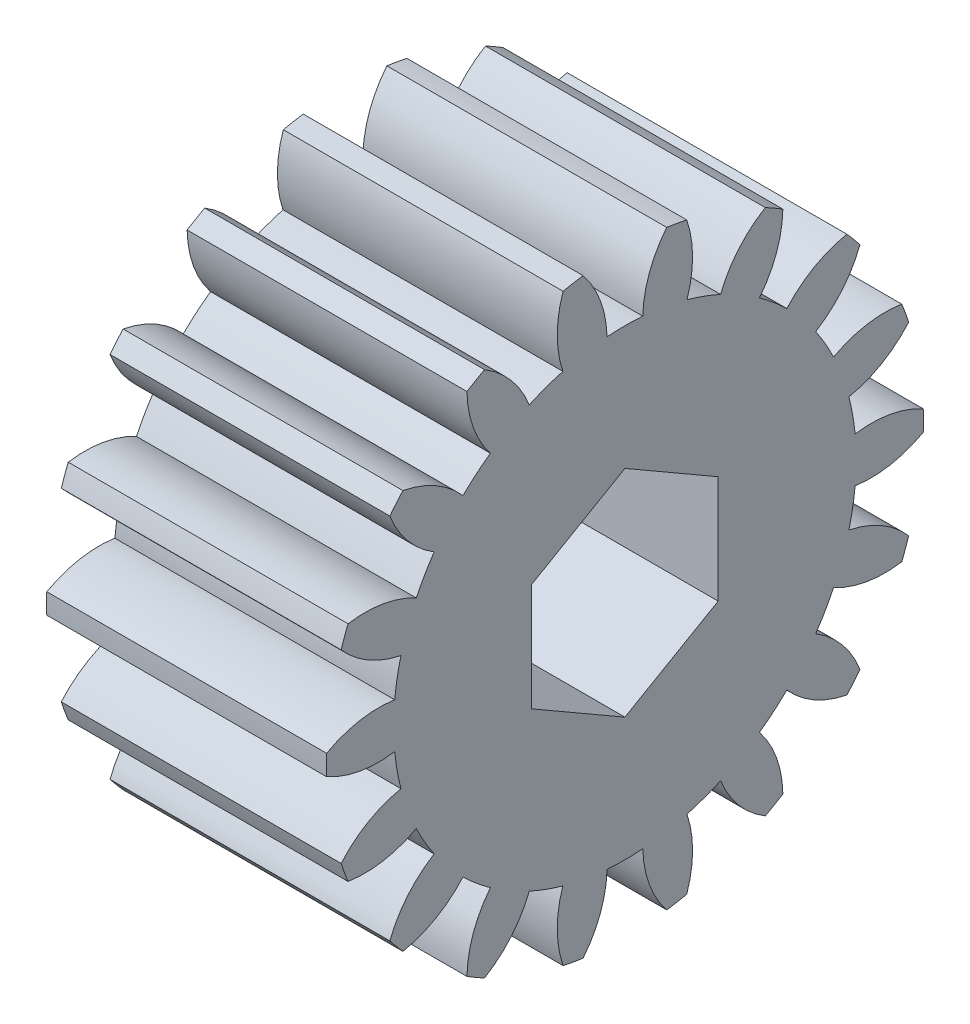
SolidWorks part; units mm, degrees
ref_plane "Plane1" through (0, 0, 0) normal (0, 0, 1) x (1, 0, 0)
ref_plane "Plane2" through (0, 0, 0) normal (0, 1, 0) x (1, 0, 0)
ref_plane "Plane3" through (0, 0, 0) normal (1, 0, 0) x (0, 0, -1)
other "Configuration Table"
sketch "HoldingSke" plane through (0, 0, 0) normal (0, 1, 0) x (1, 0, 0)
  line L0 (0, 0) -> (1.1888, -0.3863)
  line L1 (-15, 0) -> (100, 0) construction
  line L2 (0, 0) -> (-2.1039, 2.3779)
  line L3 (0, 0) -> (-11.863, 4.5341)
  line L4 (0, 0) -> (8.2133, 2.6687)
  line L5 (0, 0) -> (-46.8476, -17.4728)
  line L6 (0, 0) -> (-6.2172, -4.1948)
  line L7 (-2.1039, 2.3779) -> (8.6586, 51.2059)
  line L8 (-76.2, 54.61) -> (-75.3, 54.61)
  line L9 (-67.7845, 28.3722) -> (-49.3413, 33.142)
  line L10 (-76.2, 71.12) -> (104.1128, 71.12)
  line L11 (0, 0) -> (-7.5, 0)
  line L12 (-76.2, 101.6) -> (-76.17, 101.6)
  line L13 (24.9733, 27.94) -> (52.9518, 28.4284)
  line L14 (24.9733, 27.94) -> (24.9743, 27.94)
  line L15 (24.9733, 27.94) -> (100.4006, 29.5858)
  line L16 (-63.627, -0.8) -> (-12.827, -0.8)
  circle A0 centre (0, 0) radius 2.5
  circle A1 centre (0, 0) radius 6.199
  circle A2 centre (0, 0) radius 37.5
  circle A3 centre (0, 0) radius 2.5
  dimension "MHD" = 12.398
  dimension "Hub_dia" = 75
  dimension "Bore" = 5
  dimension "MBD" = 5
  dimension "Num_teeth" = 18
  dimension "Pitch" = 1.25
  dimension "Overall_len" = 50
  dimension "Show_teeth" = 18
  dimension "Thickness" = 7.5
  dimension "OAL" = 50.0001
  dimension "T_dim" = 0.9
  dimension "Ap" = 14.5
  dimension "H" = 19.05
  dimension "Pitch_radius" = 180.3128
  dimension "Width" = 7.5
  dimension "Backlash" = 0.03
  dimension "Addendum_fac" = 1
  dimension "Dedendum_fac" = 1.25
  dimension "Clearance_fac" = 0.25
  dimension "Dedendum_add" = 0.001
  dimension "Module" = 0.8
sketch "BasProSke" plane through (0, 0, 0) normal (0, 1, 0) x (1, 0, 0)
  line L0 (-10, 0) -> (60, 0) construction
  line L1 (0, 0) -> (0, 8)
  line L2 (0, 0) -> (7.5, 0)
  line L3 (7.5, 0) -> (7.5, 8)
  line L4 (7.5, 8) -> (0, 8)
  dimension "Thickness" = 7.5
  dimension "Diameter" = 16
revolve "Base-Revolve" add sketch "BasProSke" angle 360 about L0
sketch "TooCutSke" plane through (0, 0, 0) normal (1, 0, 0) x (0, 0, -1)
  line L1 (0, 0) -> (0, 107) construction
  line L2 (0, 0) -> (-0.68, 7.1678) construction
  line L3 (0, 0) -> (-2.4925, 14.1359) construction
  line L4 (-0.68, 7.1678) -> (-1.2463, 7.068) construction
  arc A0 (0.479, 6.1805) -> (-0.479, 6.1805) centre (0, 0) ccw
  arc A1 (1.1389, 7.9442) -> (-1.1389, 7.9442) centre (0, 0) ccw
  circle A2 centre (0, 0) radius 7.2 construction
  circle A3 centre (0, 0) radius 6.9707 construction
  arc A4 (-0.479, 6.1805) -> (-1.1389, 7.9442) centre (-3.3581, 6.1085) ccw
  arc A5 (1.1389, 7.9442) -> (0.479, 6.1805) centre (3.3581, 6.1085) ccw
  dimension "Root_dia" = 12.398
  dimension "Overcut_dia" = 16.0508
  dimension "Pitch_dia" = 14.4
  dimension "Base_dia" = 13.9413
  dimension "Flank_rad" = 2.88
  dimension "Half_ang" = 10
  dimension "Half_CT" = 0.575
extrude "ToothCut" cut sketch "TooCutSke" along normal through all
fillet "Breaks" [suppressed] radius 0.016 tangent propagation no
fillet "RootFillets" [suppressed] radius 0.201
pattern_circular "TeethCuts" count 18 every 20 about axis through (-10, 0, 0) along (1, 0, 0) of "ToothCut", "RootFillets", "Breaks"
sketch "HubNeaOneSke" plane through (0, 0, 0) normal (-1, 0, 0) x (0, 0, 1)
  circle A0 centre (0, 0) radius 6.199
  dimension "Diameter" = 12.398
extrude "HubNearOne" [suppressed] add sketch "HubNeaOneSke" along normal blind 42.5001
sketch "HubNeaBotSke" plane through (0, 0, 0) normal (-1, 0, 0) x (0, 0, 1)
  circle A0 centre (0, 0) radius 6.199
  dimension "Diameter" = 12.398
extrude "HubNearBoth" [suppressed] add sketch "HubNeaBotSke" along normal blind 21.25
ref_plane "FarPln" through (7.5, 0, 0) normal (1, 0, 0) x (0, 0, -1)
sketch "HubFarSke" plane through (7.5, 0, 0) normal (1, 0, 0) x (0, 0, -1)
  circle A0 centre (0, 0) radius 6.199
  dimension "Diameter" = 12.398
extrude "HubFar" [suppressed] add sketch "HubFarSke" along normal blind 21.25
sketch "BorSke" plane through (0, 0, 0) normal (1, 0, 0) x (0, 0, -1)
  circle A0 centre (0, 0) radius 2.5
  dimension "Diameter" = 5
extrude "Bore" cut sketch "BorSke" along normal mid plane 100.0001
sketch "KeySke" plane through (0, 0, 0) normal (1, 0, 0) x (0, 0, -1)
  line L0 (-1, 0) -> (-1, 3.4)
  line L1 (-1, 3.4) -> (1, 3.4)
  line L2 (1, 3.4) -> (1, 0)
  line L3 (0, 0) -> (0, 34) construction
  line L4 (-1, 0) -> (1, 0)
  dimension "Offset" = 3.4
  dimension "Width" = 2
extrude "Keyway" [suppressed] cut sketch "KeySke" along normal mid plane 100.0001
pattern_circular "Keyway2" [suppressed] count 2 every 90 about axis through (-10, 0, 0) along (1, 0, 0) reverse direction yes
sketch "Schizzo2" plane through (7.5, 0, 0) normal (1, 0, 0) x (0, 0, -1)
  line L1 (0, 2.8868) -> (-2.5, 1.4434)
  line L2 (-2.5, 1.4434) -> (-2.5, -1.4434)
  line L3 (-2.5, -1.4434) -> (0, -2.8868)
  line L4 (0, -2.8868) -> (2.5, -1.4434)
  line L5 (2.5, -1.4434) -> (2.5, 1.4434)
  line L6 (2.5, 1.4434) -> (0, 2.8868)
  circle A0 centre (0, 0) radius 2.5 construction
extrude "Taglio-Estrusione1" cut sketch "Schizzo2" against normal blind 10
equation "' \"Module@HoldingSke\" = 6.35"
equation "' \"Num_teeth@HoldingSke\" = 12"
equation "' \"Ap@HoldingSke\" =  20"
equation "' \"Ap@HoldingSke\" = 20"
equation "' \"Width@HoldingSke\" = 0.5 * 25.4"
equation "' \"Hub_dia@HoldingSke\"= 1 * 25.4"
equation "' \"Hub_dia@HoldingSke\" = 1 * 25.4"
equation "' \"Overall_len@HoldingSke\" = 1.0 * 25.4"
equation "' \"Bore@HoldingSke\" = 0.75 * 25.4"
equation "' \"T_dim@HoldingSke\" = 0.1 * 25.4"
equation "' \"Width@KeySke\" = 0.25 * 25.4"
equation "' \"Show_teeth@HoldingSke\" = 13"
equation "' \"Backlash@HoldingSke\" = 0.009 * 25.4"
equation "' \"Addendum_fac@HoldingSke\" = 1.0"
equation "' \"Dedendum_fac@HoldingSke\" = 1.25"
equation "' \"Dedendum_add@HoldingSke\" = 0.00005 * 25.4"
equation "' \"Clearance_fac@HoldingSke\" = 0.25"
equation "\"Pitch@HoldingSke\" = 1 / \"Module@HoldingSke\""
equation "\"Overcut_dia@TooCutSke\" = (\"Num_teeth@HoldingSke\" + 2 * \"Addendum_fac@HoldingSke\") / \"Pitch@HoldingSke\" + 0.002 * 25.4"
equation "\"Pitch_dia@TooCutSke\" = \"Num_teeth@HoldingSke\" / \"Pitch@HoldingSke\""
equation "\"Base_dia@TooCutSke\" = \"Num_teeth@HoldingSke\" / \"Pitch@HoldingSke\" * cos((\"Ap@HoldingSke\"  * 3.14159265 / 180))"
equation "\"Root_dia@TooCutSke\" = (\"Num_teeth@HoldingSke\" + 2) / \"Pitch@HoldingSke\" - 2 * (\"Addendum_fac@HoldingSke\" + \"Dedendum_fac@HoldingSke\") / \"Pitch@HoldingSke\" - \"Dedendum_add@HoldingSke\" * 2"
equation "\"Half_ang@TooCutSke\" = 180 / \"Num_teeth@HoldingSke\""
equation "\"Half_CT@TooCutSke\" = \"Num_teeth@HoldingSke\" / \"Pitch@HoldingSke\" * sin((3.14159265 / 2 / \"Num_teeth@HoldingSke\")) / 2 - 7 * \"Backlash@HoldingSke\" / 4"
equation "\"Flank_rad@TooCutSke\" = \"Num_teeth@HoldingSke\" / \"Pitch@HoldingSke\" / 5"
equation "\"Radius@RootFillets\" = \"Clearance_fac@HoldingSke\" / \"Pitch@HoldingSke\" + \"Dedendum_add@HoldingSke\""
equation "\"Break_rad@Breaks\" = 0.02 / \"Pitch@HoldingSke\""
equation "\"Thickness@HoldingSke\" = \"Width@HoldingSke\""
equation "\"OAL@HoldingSke\" = \"Thickness@HoldingSke\""
equation "\"MHD@HoldingSke\" = (\"Num_teeth@HoldingSke\" + 2) / \"Pitch@HoldingSke\" - 2 * (\"Addendum_fac@HoldingSke\" + \"Dedendum_fac@HoldingSke\")  / \"Pitch@HoldingSke\" - \"Dedendum_add@HoldingSke\" * 2"
equation "\"MBD@HoldingSke\" = (\"Num_teeth@HoldingSke\" + 2) / \"Pitch@HoldingSke\" - 2 * (\"Addendum_fac@HoldingSke\" + \"Dedendum_fac@HoldingSke\")  / \"Pitch@HoldingSke\" - \"Dedendum_add@HoldingSke\" * 2 - 0.002 * 25.4"
equation "\"MHD@HoldingSke\" = ((sgn( \"MHD@HoldingSke\" - \"Hub_dia@HoldingSke\" )-1)*( \"MHD@HoldingSke\" - \"Hub_dia@HoldingSke\" ))/-2+ \"Hub_dia@HoldingSke\""
equation "\"MBD@HoldingSke\" = ((sgn( \"MBD@HoldingSke\" - \"Bore@HoldingSke\" )-1)*( \"MBD@HoldingSke\" - \"Bore@HoldingSke\" ))/-2+ \"Bore@HoldingSke\""
equation "\"OAL@HoldingSke\" = ((sgn( \"OAL@HoldingSke\" - \"Overall_len@HoldingSke\" )+1)*( \"OAL@HoldingSke\" - \"Overall_len@HoldingSke\" ))/2 + \"Overall_len@HoldingSke\" + 0.000002 * 25.4"
equation "\"Num_teeth@TeethCuts\" = int( \"Show_teeth@HoldingSke\" ) + 1"
equation "\"Num_teeth@TeethCuts\" = ((sgn( \"Num_teeth@TeethCuts\" - \"Num_teeth@HoldingSke\" )-1)*( \"Num_teeth@TeethCuts\" - \"Num_teeth@HoldingSke\" ))/-2+ \"Num_teeth@HoldingSke\""
equation "\"Num_teeth@TeethCuts\" = ((sgn( \"Num_teeth@TeethCuts\" - 2.0)+1)*( \"Num_teeth@TeethCuts\" - 2.0))/2 +2.0"
equation "\"Angle@TeethCuts\" = 360.0 / \"Num_teeth@HoldingSke\""
equation "\"Diameter@BasProSke\" = (\"Num_teeth@HoldingSke\" + 2 * \"Addendum_fac@HoldingSke\") / \"Pitch@HoldingSke\""
equation "\"Thickness@BasProSke\"  = \"Thickness@HoldingSke\""
equation "' \"Fillet_rad@BasProSke\" =  \"Thickness@HoldingSke\" * 0.05"
equation "' \"Fillet_rad@BasProSke\" = \"Thickness@HoldingSke\" * 0.05"
equation "\"MHD@HoldingSke\" = ((sgn( \"MHD@HoldingSke\" - \"Root_dia@TooCutSke\" )-1)*( \"MHD@HoldingSke\" - \"Root_dia@TooCutSke\" ))/-2+ \"Root_dia@TooCutSke\""
equation "\"Diameter@HubNeaOneSke\" = \"MHD@HoldingSke\""
equation "\"Length@HubNearOne\" = \"OAL@HoldingSke\" - \"Thickness@BasProSke\""
equation "\"Diameter@HubNeaBotSke\" = \"MHD@HoldingSke\""
equation "\"Length@HubNearBoth\" = ( \"OAL@HoldingSke\" - \"Thickness@BasProSke\" ) / 2.0"
equation "\"Thickness@FarPln\" = \"Thickness@BasProSke\""
equation "\"Diameter@HubFarSke\" = \"MHD@HoldingSke\""
equation "\"Length@HubFar\" = ( \"OAL@HoldingSke\" - \"Thickness@BasProSke\" ) / 2.0"
equation "\"Diameter@BorSke\" = \"MBD@HoldingSke\""
equation "\"D1@Bore\" = \"OAL@HoldingSke\" * 2.0"
equation "\"D1@Keyway\" = \"OAL@HoldingSke\" * 2.0"
equation "\"Offset@KeySke\" = \"T_dim@HoldingSke\" + \"MBD@HoldingSke\" / 2.0"
